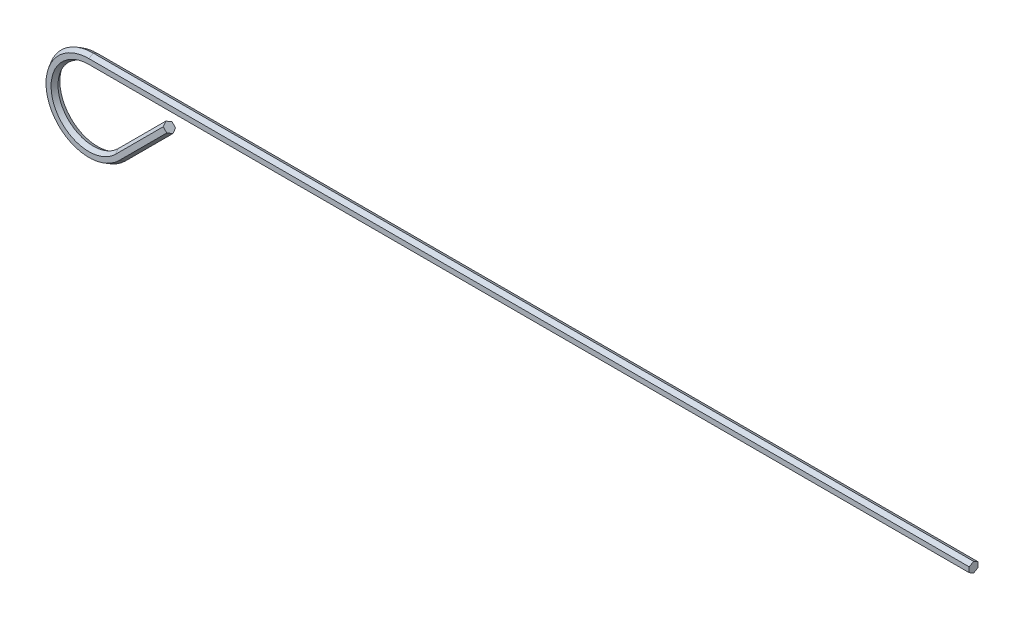
SolidWorks part; units mm, degrees
material "PW20:29:Sc:0:"
ref_plane "Front" through (0, 0, 0) normal (0, 0, 1) x (1, 0, 0)
ref_plane "Top" through (0, 0, 0) normal (0, 1, 0) x (1, 0, 0)
ref_plane "Right" through (0, 0, 0) normal (1, 0, 0) x (0, 0, -1)
sketch "Sketch1" plane through (0, 0, 0) normal (0, 0, 1) x (1, 0, 0)
  line L0 (100, 4) -> (0, 4)
  line L1 (2.8284, -2.8284) -> (8.2426, 2.5858)
  line L2 (8.2426, 2.5858) -> (9.6569, 4) construction
  arc A0 (0, 4) -> (2.8284, -2.8284) centre (0, 0) ccw
  dimension "Center_Rad" = 4
  dimension "Length" = 100
  dimension "Overlap" = 2
  dimension "Angle" = 45
ref_plane "Plane4" through (100, 4, 0) normal (-1, 0, 0) x (0, 0, 1)
sketch "Sketch2" plane through (100, 4, 0) normal (-1, 0, 0) x (0, 0, 1)
  line L0 (0, 0) -> (0, 1.1547) construction
  line L1 (-0.5, 0.866) -> (0, 1.1547)
  line L2 (-0.5, 0.2887) -> (-0.5, 0.866)
  line L3 (0, 0) -> (0.5, 0.2887)
  line L4 (0.5, 0.2887) -> (0.5, 0.866)
  line L5 (0.5, 0.866) -> (0, 1.1547)
  line L6 (0, 0) -> (-0.5, 0.2887)
  line L7 (0.5, 0.2887) -> (-0.5, 0.866) construction
  line L8 (0.5, 0.866) -> (-0.5, 0.2887) construction
  dimension "Hex_Diam" = 1
sweep "Base-Sweep" add profiles "Sketch2" path "Sketch1"
ref_axis "center_axis" [suppressed] through (0, 0, 50.5) along (0, 0, -1)
